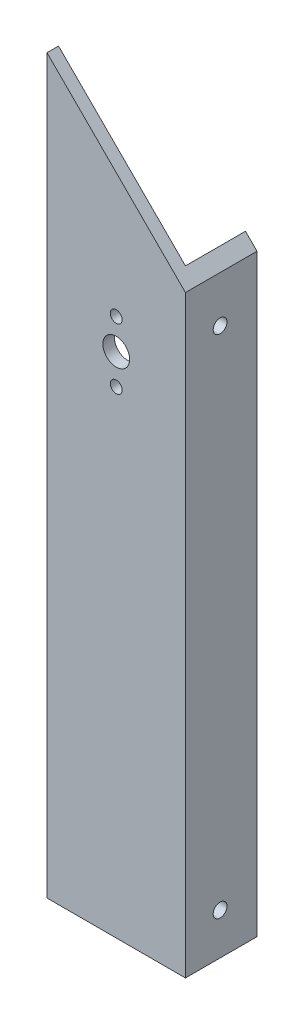
SolidWorks part; units mm, degrees
ref_plane "Front Plane" through (0, 0, 0) normal (0, 0, 1) x (1, 0, 0)
ref_plane "Top Plane" through (0, 0, 0) normal (0, 1, 0) x (1, 0, 0)
ref_plane "Right Plane" through (0, 0, 0) normal (1, 0, 0) x (0, 0, -1)
sketch "Sketch1" plane through (0, 0, 0) normal (0, 1, 0) x (1, 0, 0)
  line L0 (0, 0) -> (-38.1, 0)
  line L1 (-38.1, 0) -> (-38.1, 3.175)
  line L2 (-38.1, 3.175) -> (-3.175, 3.175)
  line L3 (-3.175, 3.175) -> (-3.175, 19.685)
  line L4 (-3.175, 19.685) -> (0, 19.685)
  line L5 (0, 19.685) -> (0, 0)
  dimension "D1" = 16.51
  dimension "D2" = 3.175
  dimension "D3" = 38.1
extrude "Boss-Extrude1" add sketch "Sketch1" along normal blind 203.2 contours L2 L3 L4 L5 L0 L1
sketch "Sketch4" plane through (0, 0, 0) normal (0, 0, 1) x (1, 0, 0)
  line L0 (0, 203.2) -> (0, 0) construction
  line L1 (-38.1, 201.422) -> (-57.2505, 201.422)
  line L2 (-38.1, 201.422) -> (0, 163.322)
  line L3 (-38.1, 203.2) -> (-38.1, 0) construction
  line L5 (14.4916, 163.322) -> (14.4916, 247.072)
  line L6 (14.4916, 247.072) -> (-57.2505, 247.072)
  line L7 (-57.2505, 247.072) -> (-57.2505, 201.422)
  line L9 (0, 163.322) -> (14.4916, 163.322)
  dimension "D1" = 163.322
  dimension "D2" = 135
extrude "Cut-Extrude2" cut sketch "Sketch4" against normal through all contours L7 L1 L2 L9 L5 L6
sketch "Sketch5" plane through (0, 0, 0) normal (0, 0, 1) x (1, 0, 0)
  line L0 (-19.05, 148.082) -> (-19.05, 131.318) construction
  line L1 (0, 0) -> (-38.1, 0) construction
  line L2 (0, 139.7) -> (-38.1, 139.7) construction
  line L3 (0, 163.322) -> (0, 0) construction
  line L4 (-38.1, 201.422) -> (-38.1, 0) construction
  circle A0 centre (-19.05, 139.7) radius 3.683
  circle A1 centre (-19.05, 148.082) radius 1.632
  circle A2 centre (-19.05, 131.318) radius 1.632
  point P4 (-19.05, 139.7)
  point P15 (-19.05, 139.7)
  dimension "D1" = 7.366
  dimension "D2" = 3.2639
  dimension "D3" = 139.7
  dimension "D4" = 16.764
extrude "Cut-Extrude3" cut sketch "Sketch5" against normal through all
sketch "Sketch6" plane through (0, 0, 0) normal (1, 0, 0) x (0, 0, -1)
  line L0 (3.175, -1.27) -> (168.275, -1.27) construction
  line L1 (19.685, 163.322) -> (0, 163.322) construction
  circle A0 centre (9.5305, 11.43) radius 1.8986
  circle A1 centre (9.5305, 150.622) radius 1.8987
  dimension "D1" = 3.7973
  dimension "D4" = 3.7973
  dimension "D2" = 12.7
  dimension "D3" = 12.7
extrude "Cut-Extrude4" cut sketch "Sketch6" against normal through all
